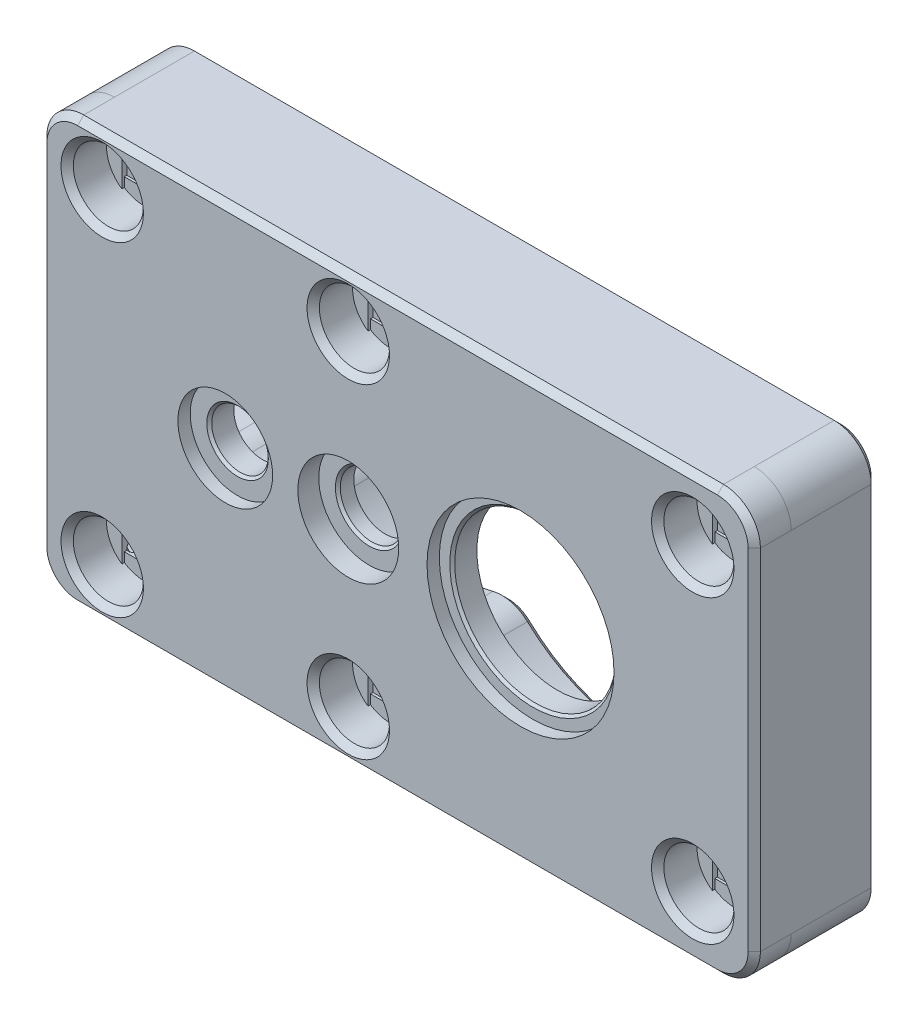
SolidWorks part; units mm, degrees
ref_plane "Front Plane" through (0, 0, 0) normal (0, 0, 1) x (1, 0, 0)
ref_plane "Top Plane" through (0, 0, 0) normal (0, 1, 0) x (1, 0, 0)
ref_plane "Right Plane" through (0, 0, 0) normal (1, 0, 0) x (0, 0, -1)
sketch "Sketch1" plane through (0, 0, 0) normal (0, 0, 1) x (1, 0, 0)
  line L21 (-15, 6) -> (-15, 14.2) construction
  line L22 (-3.6056, 3) -> (-12, 3) construction
  line L23 (-12, -3) -> (-3.6056, -3) construction
  line L24 (-15, -14.2) -> (-15, -6) construction
  line L25 (40, -17.2) -> (-12, -17.2) construction
  line L26 (43, 14.2) -> (43, -14.2) construction
  line L27 (-12, 17.2) -> (40, 17.2) construction
  line L37 (-15, 6) -> (-15, 14.2)
  line L38 (-3.6056, 3) -> (-12, 3)
  line L39 (-12, -3) -> (-3.6056, -3)
  line L40 (-15, -14.2) -> (-15, -6)
  line L41 (40, -17.2) -> (-12, -17.2)
  line L42 (43, 14.2) -> (43, -14.2)
  line L43 (-12, 17.2) -> (40, 17.2)
  arc A27 (-12, 17.2) -> (-15, 14.2) centre (-12, 14.2) ccw construction
  arc A28 (-15, 6) -> (-12, 3) centre (-12, 6) ccw construction
  arc A29 (-3.6056, 3) -> (-2.0603, 3.4286) centre (-3.6056, 6) ccw construction
  arc A30 (0.1429, 3.9974) -> (2.6875, 5.2467) centre (0.25, 6.9955) ccw construction
  arc A31 (12.25, 8.7142) -> (2.6875, 5.2467) centre (10, 0) ccw construction
  arc A32 (12.25, 8.7142) -> (15.0625, 9.4404) centre (13, 11.619) ccw construction
  arc A33 (15.0625, -9.4404) -> (15.0625, 9.4404) centre (24, 0) ccw construction
  arc A34 (15.0625, -9.4404) -> (12.25, -8.7142) centre (13, -11.619) ccw construction
  arc A35 (2.6875, -5.2467) -> (12.25, -8.7142) centre (10, 0) ccw construction
  arc A36 (2.6875, -5.2467) -> (0.1429, -3.9974) centre (0.25, -6.9955) ccw construction
  arc A37 (-2.0603, -3.4286) -> (0.1429, -3.9974) centre (0, 0) ccw construction
  arc A38 (-2.0603, -3.4286) -> (-3.6056, -3) centre (-3.6056, -6) ccw construction
  arc A39 (-12, -3) -> (-15, -6) centre (-12, -6) ccw construction
  arc A40 (-15, -14.2) -> (-12, -17.2) centre (-12, -14.2) ccw construction
  arc A41 (40, -17.2) -> (43, -14.2) centre (40, -14.2) ccw construction
  arc A42 (43, 14.2) -> (40, 17.2) centre (40, 14.2) ccw construction
  arc A43 (-12, 17.2) -> (-15, 14.2) centre (-12, 14.2) ccw
  arc A87 (-15, 6) -> (-12, 3) centre (-12, 6) ccw
  arc A88 (-3.6056, 3) -> (-2.0603, 3.4286) centre (-3.6056, 6) ccw
  arc A89 (0.1429, 3.9974) -> (2.6875, 5.2467) centre (0.25, 6.9955) ccw
  arc A90 (12.25, 8.7142) -> (2.6875, 5.2467) centre (10, 0) ccw
  arc A91 (12.25, 8.7142) -> (15.0625, 9.4404) centre (13, 11.619) ccw
  arc A92 (15.0625, -9.4404) -> (15.0625, 9.4404) centre (24, 0) ccw
  arc A93 (15.0625, -9.4404) -> (12.25, -8.7142) centre (13, -11.619) ccw
  arc A94 (2.6875, -5.2467) -> (12.25, -8.7142) centre (10, 0) ccw
  arc A95 (2.6875, -5.2467) -> (0.1429, -3.9974) centre (0.25, -6.9955) ccw
  arc A96 (-2.0603, -3.4286) -> (0.1429, -3.9974) centre (0, 0) ccw
  arc A97 (-2.0603, -3.4286) -> (-3.6056, -3) centre (-3.6056, -6) ccw
  arc A98 (-12, -3) -> (-15, -6) centre (-12, -6) ccw
  arc A99 (-15, -14.2) -> (-12, -17.2) centre (-12, -14.2) ccw
  arc A100 (40, -17.2) -> (43, -14.2) centre (40, -14.2) ccw
  arc A101 (43, 14.2) -> (40, 17.2) centre (40, 14.2) ccw
  arc A102 (0.1429, 3.9974) -> (-2.0603, 3.4286) centre (0, 0) ccw construction
  arc A103 (0.1429, 3.9974) -> (-2.0603, 3.4286) centre (0, 0) ccw
extrude "Boss-Extrude1" add sketch "Sketch1" along normal up to surface (7 mm away) contours A103 A89 A90 A91 A92 A93 A94 A95 A96 A97 L39 A98 L40 A99 L41 A100 L42 A101 L43 A43 L37 A87 L38 A88
sketch "Sketch2" plane through (0, 0, 7) normal (0, 0, 1) x (1, 0, 0)
  line L1 (-15, 17.2) -> (43, 17.2)
  line L2 (-15, 17.2) -> (-15, -17.2)
  line L3 (-15, -17.2) -> (43, -17.2)
  line L4 (43, 17.2) -> (43, -17.2)
extrude "Boss-Extrude2" add sketch "Sketch2" along normal up to surface (3 mm away)
sketch "Sketch4" plane through (0, 0, 10) normal (0, 0, 1) x (1, 0, 0)
  circle A0 centre (0, 0) radius 2.3 construction
  circle A1 centre (0, 0) radius 2.3
  circle A2 centre (10, 0) radius 2.55 construction
  circle A3 centre (24, 0) radius 6.55 construction
  circle A4 centre (10, 0) radius 2.55
  circle A5 centre (24, 0) radius 6.55
extrude "Cut-Extrude1" cut sketch "Sketch4" against normal through all
sketch "Sketch5" plane through (0, 0, 10) normal (0, 0, 1) x (1, 0, 0)
  circle A0 centre (0, 0) radius 3.85
  dimension "D1" = 7.7
extrude "Cut-Extrude2" cut sketch "Sketch5" against normal blind 1 contours A0
sketch "Sketch6" plane through (0, 0, 10) normal (0, 0, 1) x (1, 0, 0)
  circle A0 centre (10, 0) radius 4.1
  dimension "D1" = 8.2
extrude "Cut-Extrude3" cut sketch "Sketch6" against normal blind 1.7
sketch "Sketch7" plane through (0, 0, 10) normal (0, 0, 1) x (1, 0, 0)
  circle A0 centre (24, 0) radius 7.6
  dimension "D1" = 15.2
extrude "Cut-Extrude4" cut sketch "Sketch7" against normal blind 1
fillet "Fillet1" radius 3 4 edges at (43, -17.2, 8.5) (-15, -17.2, 8.5) (-15, 17.2, 8.5) (43, 17.2, 8.5)
chamfer "Chamfer1" distance 0.2 angle 45 3 edges at (2.3, 0, 9) (12.55, 0, 8.3) (30.55, 0, 9)
fillet "Fillet2" radius 1 15 edges at (-14.1213, 3.8787, 7) (-7.8028, 3, 7) (-2.8038, 3.1091, 7) (-1, 3.873, 7) (1.572, 4.3025, 7) (6.9319, 8.4609, 7) (13.75, 8.7142, 7) (-14.1213, -3.8787, 7) (-7.8028, -3, 7) (-2.8038, -3.1091, 7) (-1, -3.873, 7) (1.572, -4.3025, 7) (6.9319, -8.4609, 7) (13.75, -8.7142, 7) (37, 0, 7)
sketch "Sketch8" plane through (0, 0, 0) normal (0, 0, -1) x (-1, 0, 0)
  circle A0 centre (-10, -13.2) radius 1.6 construction
  circle A1 centre (10, -13.2) radius 1.6 construction
  circle A2 centre (-10, 13.2) radius 1.6 construction
  circle A3 centre (10, 13.2) radius 1.6 construction
  circle A4 centre (-10, -13.2) radius 1.6
  circle A5 centre (10, -13.2) radius 1.6
  circle A6 centre (-10, 13.2) radius 1.6
  circle A7 centre (10, 13.2) radius 1.6
extrude "Cut-Extrude5" cut sketch "Sketch8" against normal through all
sketch "Sketch9" plane through (0, 0, 10) normal (0, 0, 1) x (1, 0, 0)
  circle A0 centre (-10, 13.2) radius 2.85
  dimension "D1" = 5.7
extrude "Cut-Extrude6" cut sketch "Sketch9" against normal blind 3.2
sketch "Sketch10" plane through (0, 0, 10) normal (0, 0, 1) x (1, 0, 0)
  point P0 (-10, 13.2)
  point P1 (10, 13.2)
  point P3 (10, -13.2)
  point P5 (-10, -13.2)
sketch "Sketch11" plane through (0, 0, 6.8) normal (0, 0, 1) x (1, 0, 0)
  line L0 (-11.6, 15.5585) -> (-11.6, 10.8415)
  line L1 (-8.4, 15.5585) -> (-8.4, 10.8415)
  circle A0 centre (-10, 13.2) radius 2.85 construction
  circle A1 centre (-10, 13.2) radius 2.85
  circle A2 centre (-10, 13.2) radius 1.6 construction
  circle M4 centre (-10, 13.2) radius 2.85
  circle M5 centre (-10, 13.2) radius 1.6
extrude "Cut-Extrude7" cut sketch "Sketch11" against normal blind 0.2 contours L1 L0 M4 M5 | M5 | L1 L0 M5 M4
sketch "Sketch12" plane through (0, 0, 6.6) normal (0, 0, 1) x (1, 0, 0)
  line L0 (-11.6, 14.8) -> (-8.4, 14.8)
  line L1 (-11.6, 15.5585) -> (-11.6, 13.2) construction
  line L2 (-8.4, 15.5585) -> (-8.4, 13.2) construction
  line L3 (-8.4, 14.8) -> (-8.4, 11.6)
  line L4 (-8.4, 13.2) -> (-8.4, 10.8415) construction
  line L5 (-8.4, 11.6) -> (-11.6, 11.6)
  line L6 (-11.6, 11.6) -> (-11.6, 14.8)
  arc A0 (-8.4, 13.2) -> (-11.6, 13.2) centre (-10, 13.2) ccw construction
  arc A1 (-11.6, 13.2) -> (-8.4, 13.2) centre (-10, 13.2) ccw construction
extrude "Cut-Extrude8" cut sketch "Sketch12" against normal blind 0.2
pattern_sketch "Sketch-Pattern1" of "Cut-Extrude6", "Cut-Extrude7", "Cut-Extrude8" driven by "Sketch10"
sketch "Sketch13" plane through (0, 0, 10) normal (0, 0, 1) x (1, 0, 0)
  point P0 (38, 12.2)
  point P1 (38, -12.2)
sketch "Sketch15" plane through (0, 0, 10) normal (0, 0, 1) x (1, 0, 0)
  circle A0 centre (38, 12.2) radius 1.6 construction
  circle A1 centre (38, -12.2) radius 1.6 construction
  circle A3 centre (38, 12.2) radius 1.6
  circle A5 centre (38, -12.2) radius 1.6
extrude "Cut-Extrude9" cut sketch "Sketch15" against normal through all
pattern_sketch "Sketch-Pattern3" of "Cut-Extrude6", "Cut-Extrude7", "Cut-Extrude8" driven by "Sketch13"
sketch "Sketch16" plane through (0, 0, 0) normal (0, 0, -1) x (-1, 0, 0)
  line L0 (-3, -12.7) -> (5, -12.7) construction
  line L1 (5, -12.7) -> (5, -7.7) construction
  line L2 (5, -7.7) -> (2, -7.7) construction
  line L3 (2, -7.7) -> (-3, -12.7) construction
  line L4 (-0.5858, -12.7) -> (4, -12.7) construction
  line L5 (5, -11.7) -> (5, -8.7) construction
  line L6 (4, -7.7) -> (2.4142, -7.7) construction
  line L7 (1.7071, -7.9929) -> (-1.2929, -10.9929) construction
  line L8 (4, -7.6) -> (2.4142, -7.6)
  line L9 (1.6364, -7.9222) -> (-1.3636, -10.9222)
  line L10 (-0.5858, -12.8) -> (4, -12.8)
  line L11 (5.1, -11.7) -> (5.1, -8.7)
  arc A0 (4, -12.7) -> (5, -11.7) centre (4, -11.7) ccw construction
  arc A1 (-0.5858, -12.7) -> (-1.2929, -10.9929) centre (-0.5858, -11.7) cw construction
  arc A2 (2.4142, -7.7) -> (1.7071, -7.9929) centre (2.4142, -8.7) ccw construction
  arc A3 (5, -8.7) -> (4, -7.7) centre (4, -8.7) ccw construction
  arc A4 (2.4142, -7.6) -> (1.6364, -7.9222) centre (2.4142, -8.7) ccw
  arc A5 (-0.5858, -12.8) -> (-1.3636, -10.9222) centre (-0.5858, -11.7) cw
  arc A6 (4, -12.8) -> (5.1, -11.7) centre (4, -11.7) ccw
  arc A7 (5.1, -8.7) -> (4, -7.6) centre (4, -8.7) ccw
  dimension "D1" = 1
  dimension "D2" = 0.1
extrude "Cut-Extrude10" cut sketch "Sketch16" against normal blind 3.1
fillet "Fillet3" radius 1 16 edges at (-4.7778, -7.9222, 3.1) (-5.1, -10.2, 3.1) (-4.7778, -12.4778, 3.1) (-1.7071, -12.8, 3.1) (1.6021, -12.121, 3.1) (-0.1364, -9.4222, 3.1) (-1.9933, -7.6837, 3.1) (-3.2071, -7.6, 3.1) (-4.7778, -7.9222, 0) (-5.1, -10.2, 0) (-4.7778, -12.4778, 0) (-1.7071, -12.8, 0) (1.6021, -12.121, 0) (-0.1364, -9.4222, 0) (-1.9933, -7.6837, 0) (-3.2071, -7.6, 0)
mirror "Mirror1" about plane through (0, 0, 0) normal (0, 1, 0) of "Cut-Extrude10", "Fillet3"
chamfer "Chamfer2" distance 0.5 angle 45 48 edges at (43, 0, 10) (14, -17.2, 10) (14, 17.2, 10) (-15, 0, 10) (42.1213, 16.3213, 10) (-14.1213, 16.3213, 10) (-14.1213, -16.3213, 10) (42.1213, -16.3213, 10) (-2.8038, 3.1091, 0) (-7.8028, 3, 0) (-11.6, -13.2, 0) (-14.1213, 3.8787, 0) (8.4, 13.2, 0) (-11.6, 13.2, 0) (8.4, -13.2, 0) (-15, 10.1, 0) (-14.1213, 16.3213, 0) (-7.15, 13.2, 10) (14, 17.2, 0) (42.1213, 16.3213, 0) (43, 0, 0) (42.1213, -16.3213, 0) (14, -17.2, 0) (-14.1213, -16.3213, 0) (-15, -10.1, 0) (-14.1213, -3.8787, 0) (-7.8028, -3, 0) (-2.8038, -3.1091, 0) (-1, -3.873, 0) (1.572, -4.3025, 0) (6.9319, -8.4609, 0) (-11.1314, -12.0686, 6.4) (-8.8686, -12.0686, 6.4) (-8.8686, -14.3314, 6.4) (-11.1314, -14.3314, 6.4) (13.75, -8.7142, 0) (37, 0, 0) (-7.15, -13.2, 10) (13.75, 8.7142, 0) (6.9319, 8.4609, 0) (1.572, 4.3025, 0) (12.85, -13.2, 10) (-1, 3.873, 0) (12.85, 13.2, 10) (39.6, -12.2, 0) (39.6, 12.2, 0) (40.85, 12.2, 10) (40.85, -12.2, 10)
